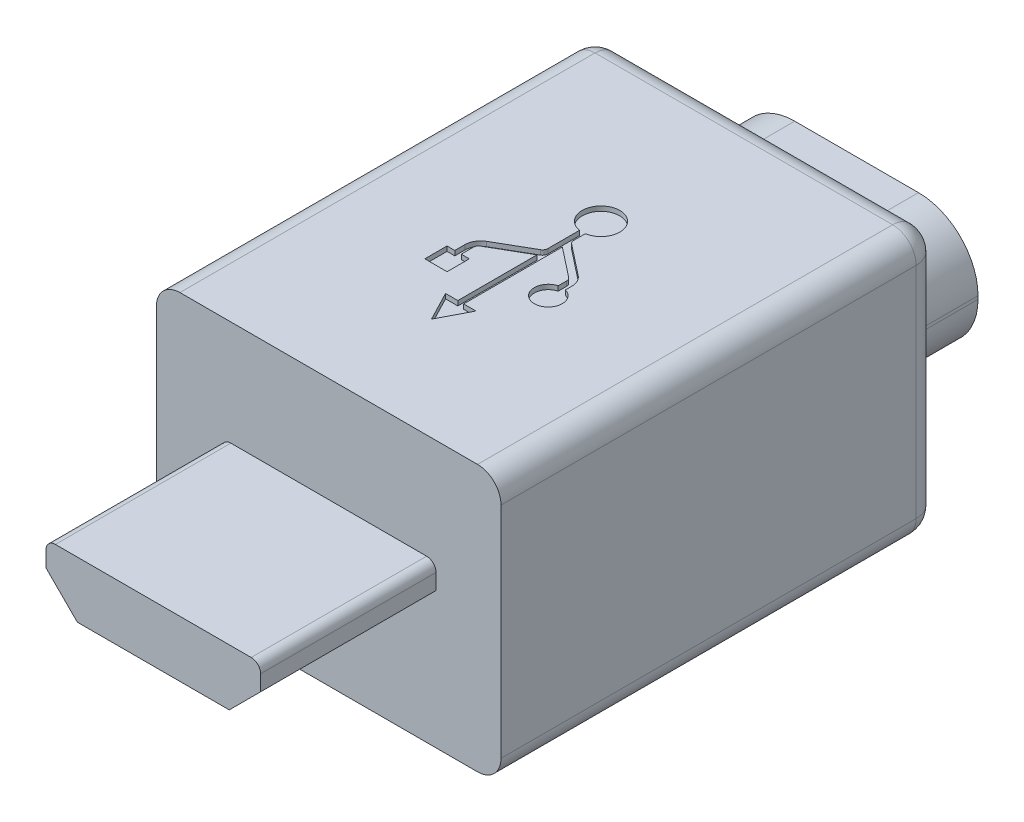
SolidWorks part; units mm, degrees
ref_plane "Front Plane" through (0, 0, 0) normal (0, 0, 1) x (1, 0, 0)
ref_plane "Top Plane" through (0, 0, 0) normal (0, 1, 0) x (1, 0, 0)
ref_plane "Right Plane" through (0, 0, 0) normal (1, 0, 0) x (0, 0, -1)
sketch "Sketch1" plane through (0, 0, 0) normal (0, 0, 1) x (1, 0, 0)
  line L1 (-5.5, -4.25) -> (5.5, -4.25)
  line L2 (-5.5, -4.25) -> (-5.5, 4.25)
  line L3 (-5.5, 4.25) -> (5.5, 4.25)
  line L4 (5.5, -4.25) -> (5.5, 4.25)
  line L5 (-5.5, -4.25) -> (5.5, 4.25) construction
  line L6 (-5.5, 4.25) -> (5.5, -4.25) construction
  point P0 (0, 0)
  dimension "D1" = 11
  dimension "D2" = 8.5
extrude "Boss-Extrude1" add sketch "Sketch1" against normal blind 14
sketch "Sketch2" plane through (0, 0, -14) normal (0, 0, -1) x (-1, 0, 0)
  line L1 (-3.875, -1.95) -> (3.875, -1.95)
  line L2 (-3.875, -1.95) -> (-3.875, 1.95)
  line L3 (-3.875, 1.95) -> (3.875, 1.95)
  line L4 (3.875, -1.95) -> (3.875, 1.95)
  line L5 (-3.875, -1.95) -> (3.875, 1.95) construction
  line L6 (-3.875, 1.95) -> (3.875, -1.95) construction
  point P0 (0, 0)
  dimension "D1" = 3.9
  dimension "D2" = 7.75
extrude "Boss-Extrude2" add sketch "Sketch2" along normal blind 2.85 contours L3 L4 L1 L2
sketch "Sketch4" plane through (0, 0, 0) normal (0, 0, 1) x (1, 0, 0)
  line L1 (-3.425, -0.9) -> (3.425, -0.9)
  line L2 (-3.425, -0.9) -> (-3.425, 0.9)
  line L3 (-3.425, 0.9) -> (3.425, 0.9)
  line L4 (3.425, -0.9) -> (3.425, 0.9)
  line L5 (-3.425, -0.9) -> (3.425, 0.9) construction
  line L6 (-3.425, 0.9) -> (3.425, -0.9) construction
  point P0 (0, 0)
  dimension "D1" = 6.85
  dimension "D2" = 1.8
extrude "Boss-Extrude4" add sketch "Sketch4" along normal blind 5.6
fillet "Fillet6" radius 0.3 2 edges at (3.425, 0.9, 2.8) (-3.425, 0.9, 2.8)
chamfer "Chamfer1" distance 1 angle 45 2 edges at (-3.425, -0.9, 2.8) (3.425, -0.9, 2.8)
sketch "Sketch5" plane through (0, -4.25, 0) normal (0, -1, 0) x (1, 0, 0)
  line L0 (0, -3.2795) -> (-0.4858, -4.2148)
  line L1 (-0.4858, -4.2148) -> (-0.0936, -4.2148)
  line L2 (-0.0936, -4.2148) -> (-0.0936, -7.3637)
  line L5 (0.0936, -8.0983) -> (0.0936, -7.0879)
  line L6 (0.0936, -4.2148) -> (0.4858, -4.2148)
  line L7 (0.4858, -4.2148) -> (0, -3.2795)
  line L8 (-0.0936, -7.7277) -> (-0.0936, -8.0983)
  line L9 (-1.329, -6.2253) -> (-1.329, -6.4288)
  line L10 (-1.1356, -6.8268) -> (-0.1581, -7.595)
  line L11 (-1.0995, -6.2253) -> (-1.0995, -6.4912)
  line L12 (-1.035, -6.6239) -> (-0.0936, -7.3637)
  line L13 (-1.329, -6.6748) -> (-1.0995, -6.5732) construction
  line L14 (1.3211, -5.5514) -> (1.3211, -5.9352)
  line L15 (1.0633, -4.8404) -> (1.7742, -4.8404)
  line L16 (1.0633, -4.8404) -> (1.0633, -5.5514)
  line L17 (1.0633, -5.5514) -> (1.3211, -5.5514)
  line L18 (1.7742, -4.8404) -> (1.7742, -5.5514)
  line L19 (1.2366, -6.0814) -> (0.0936, -6.7402)
  line L20 (1.5268, -5.5514) -> (1.5268, -5.8718)
  line L21 (1.2734, -6.3104) -> (0.1781, -6.9417)
  line L22 (1.5268, -5.5514) -> (1.7742, -5.5514)
  line L23 (0.0936, -6.7402) -> (0.0936, -4.2148)
  arc A0 (-0.0936, -8.0983) -> (0.0936, -8.0983) centre (0, -8.691) ccw
  arc A1 (-1.0995, -6.2253) -> (-1.329, -6.2253) centre (-1.2143, -5.7942) ccw
  arc A2 (-1.035, -6.6239) -> (-1.0995, -6.4912) centre (-0.9308, -6.4912) cw
  arc A3 (-0.1581, -7.595) -> (-0.0936, -7.7277) centre (-0.2624, -7.7277) cw
  arc A4 (0.0936, -7.0879) -> (0.1781, -6.9417) centre (0.2624, -7.0879) cw
  arc A5 (1.2366, -6.0814) -> (1.3211, -5.9352) centre (1.1523, -5.9352) ccw
  arc A6 (-1.1356, -6.8268) -> (-1.329, -6.4288) centre (-0.8228, -6.4288) cw
  arc A7 (1.5268, -5.8718) -> (1.2734, -6.3104) centre (1.0206, -5.8718) cw
  point P13 (-1.2143, -5.7942)
  point P31 (-0.0936, -7.6457)
extrude "Cut-Extrude1" cut sketch "Sketch5" against normal blind 0.15 contours L1 L2 L12 A2 L11 A1 L9 A6 L10 A3 L8 A0 L5 A4 L21 A7 L20 L22 L18 L15 L16 L17 L14 A5 L19 L23 L6 L7 L0
ref_axis "Axis1" through (0, 0, -122.9725) along (0, 0, 1)
pattern_circular "CirPattern1" count 2 over 360 about axis through (0, 0, -122.9725) along (0, 0, 1) of "Cut-Extrude1"
sketch "Sketch3" plane through (0, 0, -16.85) normal (0, 0, -1) x (-1, 0, 0)
  line L1 (-2.85, -0.8) -> (2.85, -0.8)
  line L2 (-2.85, -0.8) -> (-2.85, 0.8)
  line L3 (-2.85, 0.8) -> (2.85, 0.8)
  line L4 (2.85, -0.8) -> (2.85, 0.8)
  line L5 (-2.85, -0.8) -> (2.85, 0.8) construction
  line L6 (-2.85, 0.8) -> (2.85, -0.8) construction
  point P0 (0, 0)
  dimension "D1" = 5.7
  dimension "D2" = 1.6
extrude "Boss-Extrude3" [suppressed] add sketch "Sketch3" along normal blind 50
fillet "Fillet1" radius 1.9 4 edges at (-3.875, -1.95, -15.425) (-3.875, 1.95, -15.425) (3.875, -1.95, -15.425) (3.875, 1.95, -15.425)
fillet "Fillet3" radius 0.75 4 edges at (5.5, -4.25, -7) (-5.5, -4.25, -7) (-5.5, 4.25, -7) (5.5, 4.25, -7)
fillet "Fillet4" radius 0.75 8 edges at (5.2803, 4.0303, -14) (5.5, 0, -14) (5.2803, -4.0303, -14) (0, -4.25, -14) (-5.2803, -4.0303, -14) (-5.5, 0, -14) (-5.2803, 4.0303, -14) (0, 4.25, -14)
fillet "Fillet5" [suppressed] radius 0.15
